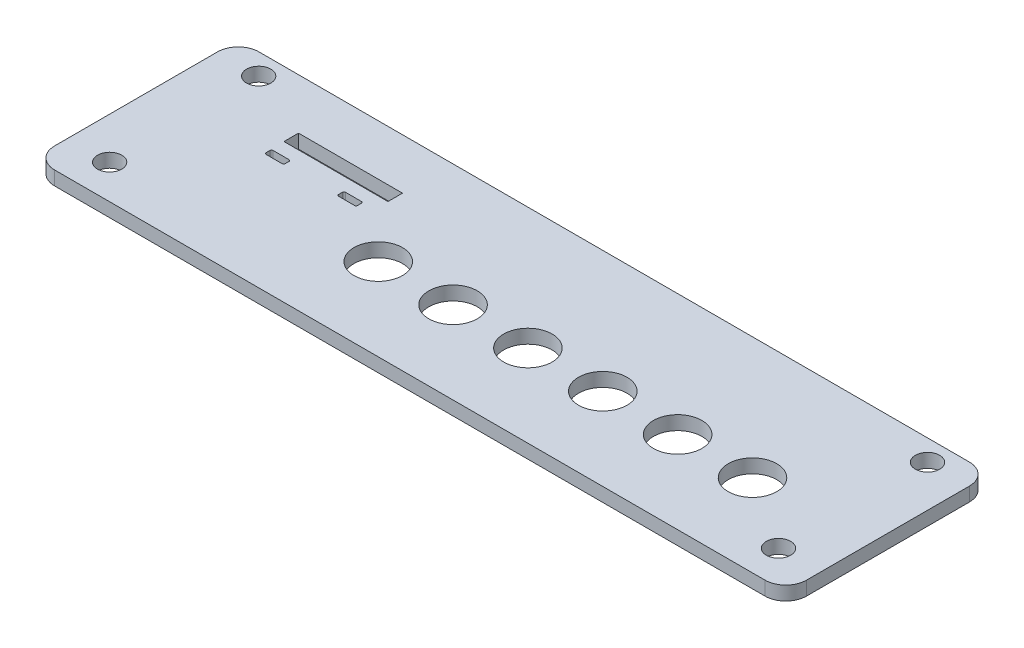
SolidWorks part; units mm, degrees
ref_plane "Front Plane" through (0, 0, 0) normal (0, 0, 1) x (1, 0, 0)
ref_plane "Top Plane" through (0, 0, 0) normal (0, 1, 0) x (1, 0, 0)
ref_plane "Right Plane" through (0, 0, 0) normal (1, 0, 0) x (0, 0, -1)
sketch "Sketch1" plane through (0, 0, 0) normal (0, 1, 0) x (1, 0, 0)
  line L1 (0, 0) -> (108.5, 0)
  line L2 (0, 0) -> (0, 29.5)
  line L3 (0, 29.5) -> (108.5, 29.5)
  line L4 (108.5, 0) -> (108.5, 29.5)
  dimension "D1" = 29.5
  dimension "D2" = 108.5
extrude "Boss-Extrude1" add sketch "Sketch1" along normal blind 2
sketch "Sketch2" plane through (0, 2, 0) normal (0, 1, 0) x (1, 0, 0)
  line L0 (54.25, 29.5) -> (54.25, 0) construction
  line L1 (108.5, 29.5) -> (0, 29.5) construction
  line L2 (0, 0) -> (108.5, 0) construction
  line L3 (0, 14.75) -> (108.5, 14.75) construction
  line L4 (0, 29.5) -> (0, 0) construction
  line L5 (108.5, 0) -> (108.5, 29.5) construction
  circle A0 centre (6, 26.45) radius 1.75
  circle A1 centre (6, 4.95) radius 1.75
  circle A2 centre (102.5, 4.95) radius 1.75
  circle A3 centre (102.5, 26.45) radius 1.75
  dimension "D1" = 3.5
  dimension "D4" = 3.5
  dimension "D2" = 48.25
  dimension "D3" = 11.7
  dimension "D5" = 9.8
  dimension "D6" = 48.25
extrude "Cut-Extrude1" cut sketch "Sketch2" against normal through all
fillet "Fillet1" radius 3 4 edges at (108.5, 1, 0) (108.5, 1, -29.5) (0, 1, 0) (0, 1, -29.5)
sketch "Sketch4" plane through (0, 2, 0) normal (0, 1, 0) x (1, 0, 0)
  line L2 (3, 0) -> (105.5, 0) construction
  line L4 (4, 7.7) -> (104.5, 7.7)
  line L5 (54.25, 29.5) -> (54.25, 0) construction
  line L6 (105.5, 29.5) -> (3, 29.5) construction
  line L7 (4, 7.7) -> (4, 9.7)
  line L8 (4, 9.7) -> (104.5, 9.7)
  line L9 (104.5, 9.7) -> (104.5, 7.7)
  dimension "D3" = 50.25
  dimension "D1" = 50.25
  dimension "D4" = 50.25
  dimension "D5" = 7.7
  dimension "D6" = 2
sketch "Sketch5" plane through (0, 2, 0) normal (0, 1, 0) x (1, 0, 0)
  line L0 (4, 9.7) -> (4, 18.2) construction
  line L1 (4, 18.2) -> (104.5, 18.2) construction
  line L2 (104.5, 18.2) -> (104.5, 9.7) construction
  line L3 (4, 20.2) -> (104.5, 20.2) construction
  line L4 (4, 18.2) -> (4, 20.2) construction
  line L5 (104.5, 18.2) -> (104.5, 20.2) construction
  line L6 (0, 26.5) -> (0, 3) construction
  line L7 (16, 20.1) -> (16, 18.2) construction
  line L8 (16, 20.1) -> (31, 20.1)
  line L9 (16, 20.1) -> (16, 22.2)
  line L10 (16, 22.2) -> (31, 22.2)
  line L11 (31, 20.1) -> (31, 22.2)
  line L13 (16.1, 18.2) -> (18.85, 18.2)
  line L14 (16.1, 18.2) -> (16.1, 17.2)
  line L15 (16.1, 17.2) -> (18.85, 17.2)
  line L16 (18.85, 18.2) -> (18.85, 17.2)
  line L17 (26.55, 18.2) -> (29.3, 18.2)
  line L18 (26.55, 18.2) -> (26.55, 17.2)
  line L19 (26.55, 17.2) -> (29.3, 17.2)
  line L20 (29.3, 18.2) -> (29.3, 17.2)
  line L27 (108.5, 3) -> (108.5, 26.5) construction
  circle A0 centre (91.8, 11.9) radius 3.5
  circle A1 centre (81, 11.9) radius 3.5
  circle A2 centre (70.2, 11.9) radius 3.5
  circle A3 centre (59.4, 11.9) radius 3.5
  circle A4 centre (48.6, 11.9) radius 3.5
  circle A5 centre (37.8, 11.9) radius 3.5
  point P24 (16, 21.15)
  point P38 (31, 21.15)
  dimension "D3" = 7
  dimension "D1" = 8.5
  dimension "D4" = 6
  dimension "D5" = 16.7
  dimension "D6" = 6.3
  dimension "D7" = 2.1
  dimension "D8" = 0.1
  dimension "D9" = 15
  dimension "D10" = 16
  dimension "D11" = 1
  dimension "D12" = 0.1
  dimension "D13" = 2.75
  dimension "D14" = 7.7
  dimension "D15" = 2.75
  dimension "D16" = 1.7
  dimension "D22" = 108.5
extrude "Cut-Extrude2" cut sketch "Sketch5" against normal through all
fillet "Fillet2" radius 0.2 8 edges at (26.55, 1, -18.2) (18.85, 1, -18.2) (29.3, 1, -18.2) (29.3, 1, -17.2) (18.85, 1, -17.2) (26.55, 1, -17.2) (16.1, 1, -17.2) (16.1, 1, -18.2)
